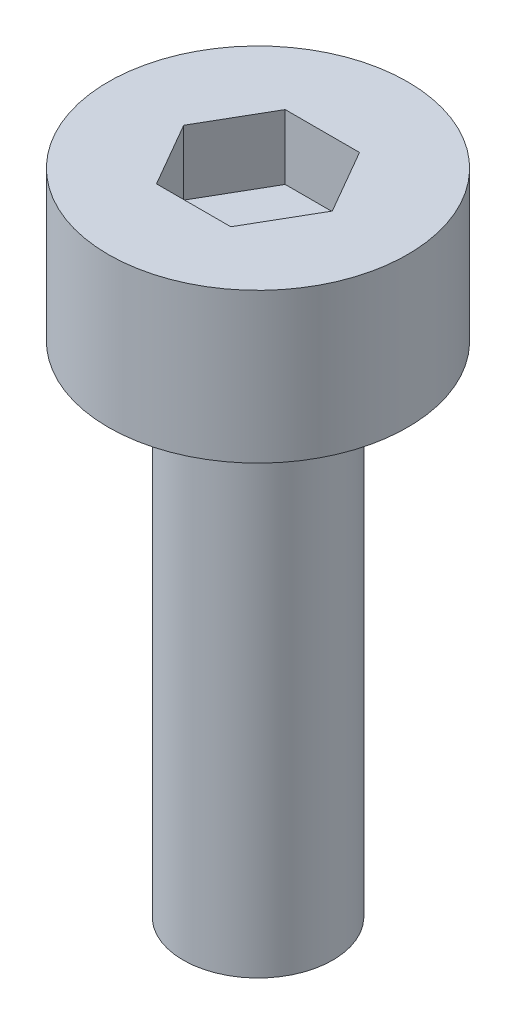
SolidWorks part; units mm, degrees
ref_plane "Front Plane" through (0, 0, 0) normal (0, 0, 1) x (1, 0, 0)
ref_plane "Top Plane" through (0, 0, 0) normal (0, 1, 0) x (1, 0, 0)
ref_plane "Right Plane" through (0, 0, 0) normal (1, 0, 0) x (0, 0, -1)
sketch "Sketch1" plane through (0, 0, 0) normal (0, 1, 0) x (1, 0, 0)
  circle A0 centre (0, 0) radius 1.5
  dimension "D1" = 3
extrude "ScrewShaft" add sketch "Sketch1" along normal blind 10
sketch "Sketch2" plane through (0, 10, 0) normal (0, 1, 0) x (1, 0, 0)
  circle A0 centre (0, 0) radius 3
  dimension "D1" = 6
extrude "Boss-Extrude2" add sketch "Sketch2" along normal blind 3
sketch "Sketch3" plane through (0, 13, 0) normal (0, 1, 0) x (1, 0, 0)
  line L0 (0, 0) -> (0, 1.29) construction
  line L1 (1.4896, 0) -> (0.7448, 1.29)
  line L2 (0.7448, 1.29) -> (-0.7448, 1.29)
  line L3 (-0.7448, 1.29) -> (-1.4896, 0)
  line L4 (-1.4896, 0) -> (-0.7448, -1.29)
  line L5 (-0.7448, -1.29) -> (0.7448, -1.29)
  line L6 (0.7448, -1.29) -> (1.4896, 0)
  circle A0 centre (0, 0) radius 1.29 construction
  dimension "D1" = 2.58
extrude "Cut-Extrude1" cut sketch "Sketch3" against normal blind 1.3
equation "\"X-ROD-SPACING\"=45"
equation "\"Y-ROD-SPACING\"=75"
equation "\"Z-ROD-SPACING\"=17.5"
equation "\"Y-BED-OFFSET\"=2"
equation "\"Y-BED-ROD-INSET\"=3.5"
equation "\"T-SLOT-NUT-FILLET-RADIUS\"=0.5"
equation "\"T-SLOT-SCREW-SHAFT-RADIUS\"=1.55"
equation "\"T-SLOT-SCREW-SHAFT-CUTOUT-LENGTH\"=11.0"
equation "\"T-SLOT-NUT-DEPTH\"=3.5"
equation "\"T-SLOT-NUT-WIDTH\"=2.85"
equation "\"T-SLOT-NUT-END-DISTANCE\"=8"
equation "\"ACRYLIC-THICKNESS\"=10"
equation "\"ACRYLIC-THICKNESS2\"=4.5"
equation "\"ACRYLIC-TAB-CUTOUT-SIZE\"=\"ACRYLIC-THICKNESS\"+\"ACRYLIC-TAB-TOLERANCE\"*2"
equation "\"ACRYLIC-TAB-WIDTH\"=\"ACRYLIC-THICKNESS\""
equation "\"ACRYLIC-M3-HOLE\"=2.9"
equation "\"SMOOTHROD-CAP-SCREW-DISTANCE\"=20"
equation "\"FRAME-WIDTH-INNER\"=370"
equation "\"NEMA17-HOLE-SPACING\"=31"
equation "\"NEMA17-CENTRAL-CUTOUT\"=22.5"
equation "\"Z-BRACKET-REACH\"=55"
equation "\"TOP-BRACKET-SPACING\"=40"
equation "\"SMOOTHROD-X-LENGTH\"=350"
equation "\"SMOOTHROD-Y-LENGTH\"=350"
equation "\"SMOOTHROD-Z-LENGTH\"=350"
equation "\"SMOOTHROD-TIGHTENING-HEADROOM\"=.25"
equation "\"LEADSCREW-Z-LENGTH\"=300"
equation "\"SCREW-LENGTH-FRAME\"=\"ACRYLIC-THICKNESS\" + 10"
equation "\"SCREW-HEAD-RADIUS\"=6"
equation "\"PRINTED-X-SMOOTHROD-DIAMETER\"=9.0"
equation "\"PRINTED-X-SMOOTHROD-CUTOUT\"=10"
equation "\"PRINTED-X-BASE-HEIGHT\"=10"
equation "\"PRINTED-LM8UU-CUTOUT-SIZE\"=15.5"
equation "\"PRINTED-LM8UU-CUTOUT-LENGTH\"=24.5"
equation "\"PRINTED-X-IDLER-HEIGHT\"=16"
equation "\"PSU-MOUNTING-WIDTH\"=95"
equation "\"PSU-MOUNTING-HEIGHT\"=177"
equation "\"D1@Sketch2\"=\"SCREW-HEAD-RADIUS\""
